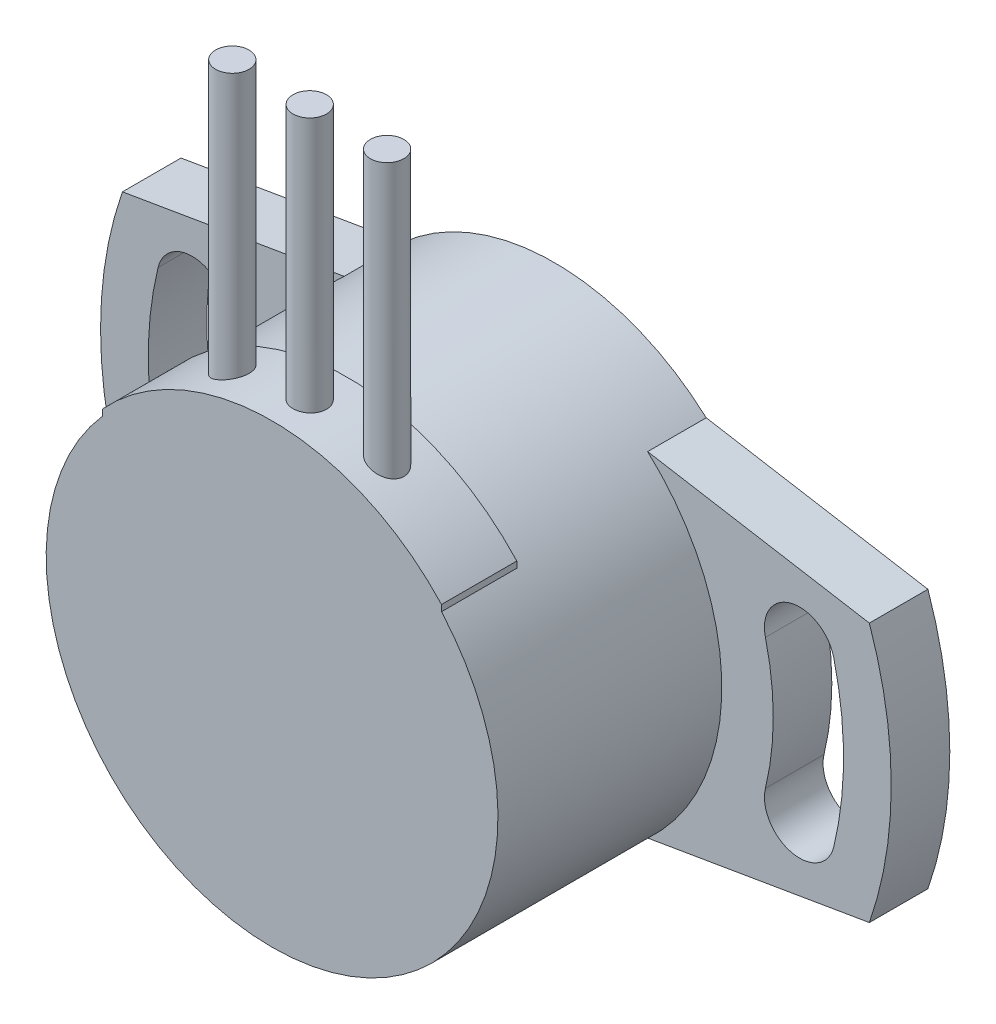
SolidWorks part; units mm, degrees
ref_plane "Front" through (0, 0, 0) normal (0, 0, 1) x (1, 0, 0)
ref_plane "Top" through (0, 0, 0) normal (0, 1, 0) x (1, 0, 0)
ref_plane "Right" through (0, 0, 0) normal (1, 0, 0) x (0, 0, -1)
sketch "Sketch1" plane through (0, 0, 0) normal (0, 0, 1) x (1, 0, 0)
  circle A0 centre (0, 0) radius 13.716
  dimension "D1" = 27.432
extrude "Boss-Extrude1" add sketch "Sketch1" along normal blind 13.589
sketch "Sketch2" plane through (0, 0, 0) normal (0, 0, -1) x (-1, 0, 0)
  line L0 (-22.6747, 7.874) -> (-9.2143, 10.16)
  line L1 (-22.6747, -7.874) -> (-9.2143, -10.16)
  line L2 (0, 0) -> (-24.003, 0) construction
  circle A0 centre (0, 0) radius 24.003
  circle A1 centre (0, 0) radius 13.716 construction
  point P9 (0, 0)
  circle M2 centre (0, 0) radius 13.716
  dimension "D1" = 48.006
  dimension "D2" = 20.32
  dimension "D3" = 10.16
  dimension "D4" = 15.748
extrude "Boss-Extrude2" add sketch "Sketch2" along normal blind 3.556 contours L2 L0 A0 M2 | L2 A0 L1 M2 | M2 region at (17.7184, 4.6228, 0) region at (-5.3992, 12.1855, 0) region at (17.7184, -4.6228, 0)
sketch "Sketch3" plane through (0, 0, -3.556) normal (0, 0, -1) x (-1, 0, 0)
  line L0 (-22.6747, 7.874) -> (-9.2143, 10.16) construction
  line L1 (-22.6747, -7.874) -> (-9.2143, -10.16) construction
  circle A0 centre (0, 0) radius 21.1074
  circle A1 centre (0, 0) radius 16.8402
  arc A2 (-22.6747, 7.874) -> (-22.6747, -7.874) centre (0, 0) ccw construction
  circle A3 centre (-18.4395, 4.4711) radius 2.1336
  circle A4 centre (-18.4395, -4.4711) radius 2.1336
  dimension "D1" = 2.8956
  dimension "D2" = 4.2672
  dimension "D3" = 4.064
  dimension "D4" = 4.064
extrude "Cut-Extrude1" cut sketch "Sketch3" against normal blind 3.556 contours A3 | A4 A1 A3 A0 | A4 region at (19.0055, 0, -3.556) region at (18.4395, 4.4711, -3.556) region at (18.4395, -4.4711, -3.556)
mirror "Mirror1" about plane through (0, 0, 0) normal (1, 0, 0) of "Boss-Extrude2", "Cut-Extrude1"
sketch "Sketch4" plane through (0, 0, -3.556) normal (0, 0, -1) x (-1, 0, 0)
  circle A0 centre (0, 0) radius 4.953
  dimension "D1" = 9.906
extrude "Boss-Extrude3" add sketch "Sketch4" along normal blind 4.826
sketch "Sketch5" plane through (0, 0, -8.382) normal (0, 0, -1) x (-1, 0, 0)
  circle A0 centre (0, 0) radius 3.0162
  dimension "D1" = 6.0325
extrude "Cut-Extrude2" cut sketch "Sketch5" against normal blind 2.54
sketch "Sketch7" plane through (0, 0, 13.589) normal (0, 0, 1) x (1, 0, 0)
  line L0 (10.287, 9.4519) -> (10.287, 5.9516)
  line L1 (10.287, 5.9516) -> (-10.287, 5.9516)
  line L2 (-10.287, 5.9516) -> (-10.287, 9.4519)
  line L3 (0, 0) -> (0, 13.97) construction
  circle A0 centre (0, 0) radius 13.97
  circle A1 centre (0, 0) radius 13.716 construction
  point P10 (0, 0)
  circle M4 centre (0, 0) radius 13.716
  dimension "D1" = 0.254
  dimension "D2" = 20.574
extrude "Boss-Extrude4" add sketch "Sketch7" against normal blind 4.572 contours L1 L3 L2 M4 | L3 L1 L0 M4 | L3 A0 L2 M4 | L3 L0 A0 M4 region at (10.1731, 9.2621, 13.589) region at (4.5439, 9.2624, 13.589) region at (-0.1139, 13.843, 13.589) region at (-4.5439, 9.2624, 13.589)
sketch "Sketch6" plane through (0, 0, 0) normal (0, 1, 0) x (1, 0, 0)
  line L0 (0, 0) -> (0, -11.303) construction
  line L1 (-13.716, -13.589) -> (13.716, -13.589) construction
  line L2 (-4.699, -11.303) -> (4.699, -11.303) construction
  circle A0 centre (0, -11.303) radius 1.016
  circle A1 centre (-4.699, -11.303) radius 1.016
  circle A2 centre (4.699, -11.303) radius 1.016
  dimension "D1" = 2.032
  dimension "D2" = 2.286
  dimension "D3" = 9.398
extrude "Boss-Extrude5" add sketch "Sketch6" along normal blind 29.464
